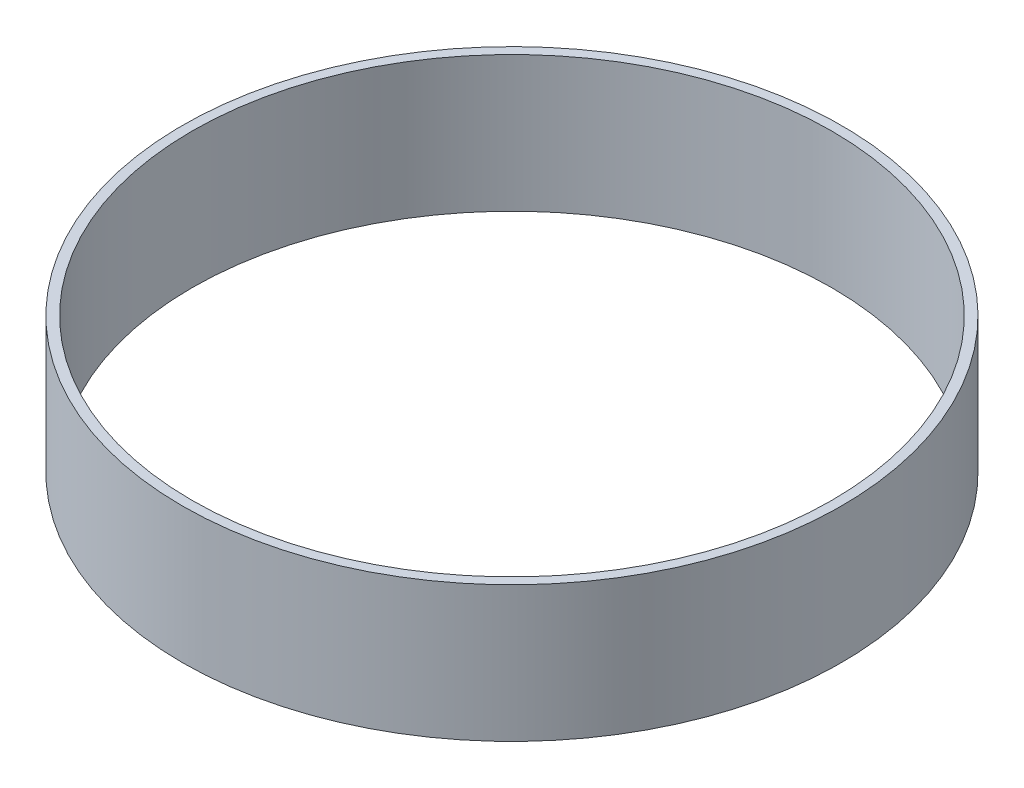
SolidWorks part; units mm, degrees
ref_plane "Front Plane" through (0, 0, 0) normal (0, 0, 1) x (1, 0, 0)
ref_plane "Top Plane" through (0, 0, 0) normal (0, 1, 0) x (1, 0, 0)
ref_plane "Right Plane" through (0, 0, 0) normal (1, 0, 0) x (0, 0, -1)
ref_axis "Axis1" through (0, 0, 0) along (0, 1, 0)
sketch "Sketch1" plane through (0, 0, 0) normal (0, 0, 1) x (1, 0, 0)
  line L0 (0, 0) -> (0, -9746.6064) construction
  line L12 (-33, -7) -> (-33, 7)
  line L13 (-33, 7) -> (-34, 7)
  line L14 (-34, 7) -> (-34, -7)
  line L20 (-34, -7) -> (-33, -7)
  point P3 (-33.25, -10.0024)
  point P5 (-33, 0)
  dimension "D1" = 14
  dimension "D2" = 68
  dimension "D3" = 66
revolve "Revolve1" add sketch "Sketch1" angle 360 about L0
